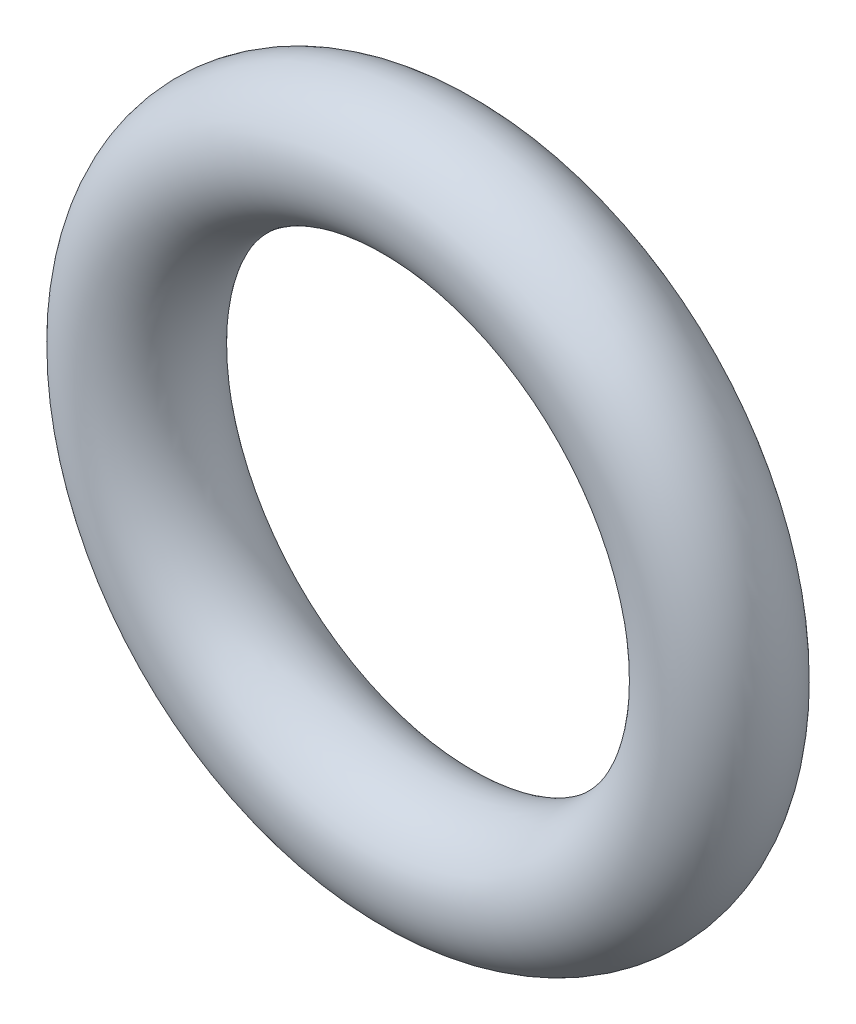
SolidWorks part; units mm, degrees
ref_plane "Front" through (0, 0, 0) normal (0, 0, 1) x (1, 0, 0)
ref_plane "Top" through (0, 0, 0) normal (0, 1, 0) x (1, 0, 0)
ref_plane "Right" through (0, 0, 0) normal (1, 0, 0) x (0, 0, -1)
sketch "Sketch1" plane through (0, 0, 0) normal (0, 0, 1) x (1, 0, 0)
  circle A0 centre (0, 0) radius 3.4
  dimension "d1" = 6.8
sketch "Sketch2" plane through (0, 0, 0) normal (0, 1, 0) x (1, 0, 0)
  circle A0 centre (-4.35, 0) radius 0.95
  point P2 (-3.4, 0)
  dimension "d2" = 1.9
sweep "Sweep1" add profiles "Sketch2" path "Sketch1"
ref_axis "Axis1" through (0, 0, -5.0798) along (0, 0, 1)
